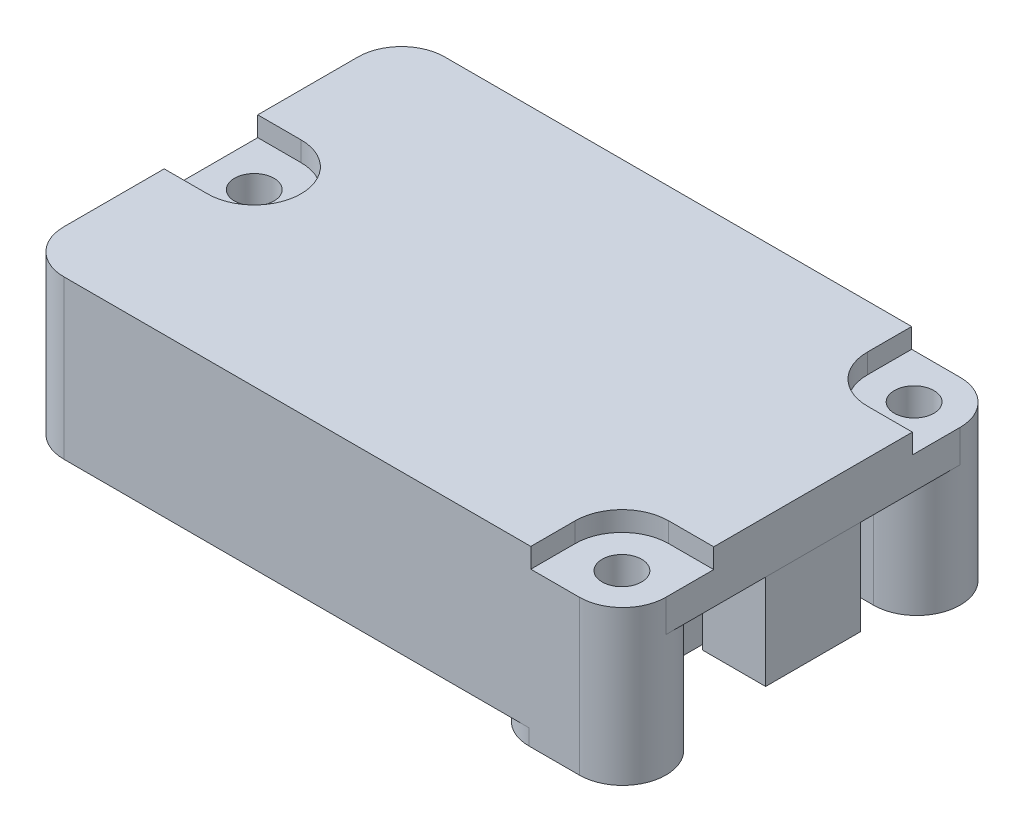
SolidWorks part; units mm, degrees
ref_plane "Ebene vorne" through (0, 0, 0) normal (0, 0, 1) x (1, 0, 0)
ref_plane "Ebene oben" through (0, 0, 0) normal (0, 1, 0) x (1, 0, 0)
ref_plane "Ebene rechts" through (0, 0, 0) normal (1, 0, 0) x (0, 0, -1)
sketch "Skizze1" plane through (0, 0, 0) normal (0, 1, 0) x (1, 0, 0)
  line L0 (-74.7889, 0) -> (82.1623, 0) construction
  line L1 (0, 57.2289) -> (0, -47.6337) construction
  line L2 (-19.05, -9.31) -> (-19.05, 9.31)
  line L3 (-16.31, 12.05) -> (16.31, 12.05)
  line L4 (19.05, -9.31) -> (19.05, 9.31)
  line L5 (-16.31, -12.05) -> (16.31, -12.05)
  arc A0 (-19.05, -9.31) -> (-16.31, -12.05) centre (-16.31, -9.31) ccw
  arc A1 (16.31, -12.05) -> (19.05, -9.31) centre (16.31, -9.31) ccw
  arc A2 (19.05, 9.31) -> (16.31, 12.05) centre (16.31, 9.31) ccw
  arc A3 (-19.05, 9.31) -> (-16.31, 12.05) centre (-16.31, 9.31) cw
  circle A4 centre (16.2, 9.245) radius 1.25
  circle A5 centre (16.2, -9.245) radius 1.25
  circle A6 centre (-16.31, 0) radius 1.25
  point P9 (0, 12.05)
  point P10 (0, -12.05)
  point P12 (19.05, 0)
  point P13 (-19.05, 0)
  point P15 (-19.05, -12.05)
  point P18 (19.05, -12.05)
  point P21 (19.05, 12.05)
  point P24 (-19.05, 12.05)
  dimension "D3" = 2.74
  dimension "D4" = 2.5
  dimension "D1" = 24.1
  dimension "D2" = 38.1
  dimension "D5" = 32.51
  dimension "D6" = 18.49
  dimension "D7" = 2.74
extrude "Aufsatz-Linear austragen1" add sketch "Skizze1" along normal blind 11
sketch "Skizze2" plane through (0, 11, 0) normal (0, 1, 0) x (1, 0, 0)
  line L0 (-27.3331, 0) -> (23.6491, 0) construction
  line L1 (0, 14.3005) -> (0, -14.3383) construction
  line L2 (-19.05, -2.96) -> (-19.05, 2.96)
  line L3 (-19.05, 9.31) -> (-19.05, -9.31) construction
  line L4 (-19.05, 2.96) -> (-16.31, 2.96)
  line L5 (-19.05, -2.96) -> (-16.31, -2.96)
  line L6 (13.24, 12.05) -> (13.24, 9.245)
  line L7 (16.31, 12.05) -> (-16.31, 12.05) construction
  line L8 (16.2, 6.285) -> (19.05, 6.285)
  line L9 (19.05, -9.31) -> (19.05, 9.31) construction
  line L10 (19.05, 6.285) -> (19.05, 12.05)
  line L11 (19.05, 12.05) -> (13.24, 12.05)
  line L12 (19.05, -12.05) -> (13.24, -12.05)
  line L13 (19.05, -6.285) -> (19.05, -12.05)
  line L14 (16.2, -6.285) -> (19.05, -6.285)
  line L15 (13.24, -12.05) -> (13.24, -9.245)
  arc A0 (-16.31, 2.96) -> (-16.31, -2.96) centre (-16.31, 0) cw
  arc A1 (13.24, 9.245) -> (16.2, 6.285) centre (16.2, 9.245) ccw
  arc A2 (13.24, -9.245) -> (16.2, -6.285) centre (16.2, -9.245) cw
  circle A3 centre (16.2, 9.245) radius 1.25 construction
  point P14 (-19.05, 0)
  dimension "D1" = 2.96
  dimension "D2" = 5.92
extrude "Schnitt-Linear austragen1" cut sketch "Skizze2" against normal blind 1.25
sketch "Skizze3" plane through (0, 0, 0) normal (0, -1, 0) x (1, 0, 0)
  line L0 (13.14, 9.31) -> (16.31, 9.31) construction
  line L1 (13.14, 12.05) -> (16.31, 12.05)
  line L2 (13.14, 6.57) -> (16.31, 6.57)
  line L3 (22.4487, 0) -> (-24.1785, 0) construction
  line L4 (0, 14.0689) -> (0, -11.8394) construction
  line L5 (13.14, -9.31) -> (16.31, -9.31) construction
  line L6 (13.14, -12.05) -> (16.31, -12.05)
  line L7 (13.14, -6.57) -> (16.31, -6.57)
  circle A0 centre (-16.31, 0) radius 2.75
  arc A1 (13.14, 12.05) -> (13.14, 6.57) centre (13.14, 9.31) ccw
  arc A2 (16.31, 6.57) -> (16.31, 12.05) centre (16.31, 9.31) ccw
  arc A3 (19.05, 9.31) -> (16.31, 12.05) centre (16.31, 9.31) ccw construction
  arc A4 (13.14, -12.05) -> (13.14, -6.57) centre (13.14, -9.31) cw
  arc A5 (16.31, -6.57) -> (16.31, -12.05) centre (16.31, -9.31) cw
  point P5 (14.725, 9.31)
  point P20 (14.725, -9.31)
  dimension "D1" = 5.5
  dimension "D2" = 8.65
extrude "Schnitt-Linear austragen2" cut sketch "Skizze3" against normal blind 1 flip side to cut
sketch "Skizze4" plane through (0, 1, 0) normal (0, -1, 0) x (1, 0, 0)
  line L0 (16.31, 6.57) -> (15.05, 6.57)
  line L1 (14.05, 5.57) -> (14.05, -5.57)
  line L2 (-26.2543, 0) -> (22.9869, 0) construction
  line L3 (0, 13.8383) -> (0, -13.8383) construction
  line L4 (13.14, 6.57) -> (16.31, 6.57) construction
  line L5 (19.05, 9.31) -> (19.05, -9.31)
  line L6 (16.31, -6.57) -> (15.05, -6.57)
  arc A0 (16.31, 6.57) -> (19.05, 9.31) centre (16.31, 9.31) ccw
  arc A1 (16.31, 6.57) -> (16.31, 12.05) centre (16.31, 9.31) ccw construction
  arc A2 (16.31, 6.57) -> (19.05, 9.31) centre (16.31, 9.31) ccw construction
  arc A3 (16.31, -6.57) -> (19.05, -9.31) centre (16.31, -9.31) cw
  arc A4 (15.05, -6.57) -> (14.05, -5.57) centre (15.05, -5.57) cw
  arc A5 (14.05, 5.57) -> (15.05, 6.57) centre (15.05, 5.57) cw
  point P22 (19.05, 0)
  point P23 (14.05, 0)
  point P25 (14.05, -6.57)
  point P28 (14.05, 6.57)
  dimension "D1" = 5
  dimension "D2" = 1
extrude "Schnitt-Linear austragen3" cut sketch "Skizze4" against normal offset from surface (6.7 mm away) 3.3 up to face at (-1.0863, 11, 0)
sketch "Skizze5" plane through (0, 7.7, 0) normal (0, -1, 0) x (1, 0, 0)
  line L0 (-29.1372, 0) -> (25.5239, 0) construction
  line L1 (15.049, -3) -> (15.049, 3)
  line L2 (15.049, 3) -> (19.049, 3)
  line L3 (19.05, -9.31) -> (19.05, 9.31) construction
  line L4 (19.049, 3) -> (19.049, -3)
  line L5 (15.049, -3) -> (19.049, -3)
  point P10 (19.05, 0)
  point P11 (15.049, 0)
  dimension "D1" = 6
  dimension "D2" = 4
  dimension "D3" = 0.001
extrude "Aufsatz-Linear austragen2" add sketch "Skizze5" along normal blind 6
ref_plane "Sensor Origin Offset Y" through (0, 0, -6.35) normal (0, 0, 1) x (1, 0, 0)
ref_plane "Sensor Origin Offset X" through (-11.99, 0, 0) normal (1, 0, 0) x (0, 0, -1)
ref_plane "Sensor Origin Offset z" through (0, 6.604, 0) normal (0, 1, 0) x (1, 0, 0)
ref_axis "Achse1" through (-11.99, 11.55, -6.35) along (0, -1, 0)
ref_axis "Achse2" through (-11.99, 6.604, 13.255) along (0, 0, -1)
ref_axis "Achse3" through (-20.955, 6.604, -6.35) along (1, 0, 0)
